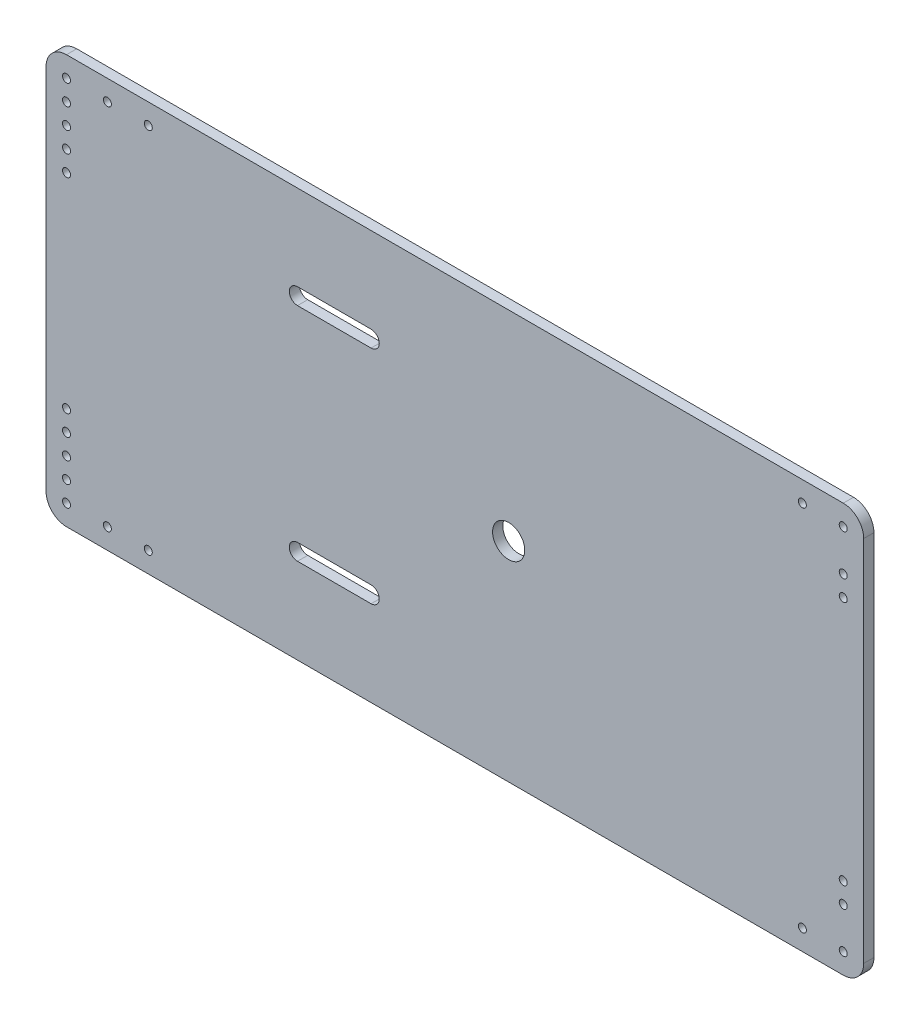
SolidWorks part; units mm, degrees
material "PC High Viscosity"
ref_plane "Front Plane" through (0, 0, 0) normal (0, 0, 1) x (1, 0, 0)
ref_plane "Top Plane" through (0, 0, 0) normal (0, 1, 0) x (1, 0, 0)
ref_plane "Right Plane" through (0, 0, 0) normal (1, 0, 0) x (0, 0, -1)
sketch "Sketch1" plane through (0, 0, 0) normal (0, 0, 1) x (1, 0, 0)
  line L1 (12.7, 0) -> (495.3, 0)
  line L2 (0, 12.7) -> (0, 241.3)
  line L3 (12.7, 254) -> (495.3, 254)
  line L4 (508, 12.7) -> (508, 241.3)
  arc A0 (495.3, 254) -> (508, 241.3) centre (495.3, 241.3) cw
  arc A1 (495.3, 0) -> (508, 12.7) centre (495.3, 12.7) ccw
  arc A2 (12.7, 0) -> (0, 12.7) centre (12.7, 12.7) cw
  arc A3 (0, 241.3) -> (12.7, 254) centre (12.7, 241.3) cw
  point P7 (508, 254)
  point P10 (508, 0)
  point P13 (0, 0)
  point P16 (0, 254)
  dimension "D3" = 12.7
  dimension "D1" = 508
  dimension "D2" = 254
extrude "Boss-Extrude1" add sketch "Sketch1" along normal blind 6.35
sketch "Sketch2" plane through (0, 0, 6.35) normal (0, 0, 1) x (1, 0, 0)
  line L10 (495.3, 254) -> (12.7, 254) construction
  line L11 (0, 241.3) -> (0, 12.7) construction
  line L12 (-20.2403, 127) -> (522.5431, 127) construction
  circle A6 centre (12.7, 190.5) radius 2.5
  circle A7 centre (12.7, 203.2) radius 2.5
  circle A8 centre (12.7, 215.9) radius 2.5
  circle A9 centre (12.7, 228.6) radius 2.5
  circle A10 centre (12.7, 241.3) radius 2.4892
  circle A11 centre (38.1, 241.3) radius 2.4892
  circle A12 centre (63.5, 241.3) radius 2.4892
  circle A13 centre (63.5, 12.7) radius 2.4892
  circle A14 centre (38.1, 12.7) radius 2.4892
  circle A15 centre (12.7, 63.5) radius 2.5
  circle A16 centre (12.7, 50.8) radius 2.5
  circle A17 centre (12.7, 38.1) radius 2.5
  circle A18 centre (12.7, 25.4) radius 2.5
  circle A19 centre (12.7, 12.7) radius 2.4892
  dimension "D2" = 12.7
  dimension "D3" = 5
  dimension "D4" = 4.9784
  dimension "D5" = 4.9784
  dimension "D6" = 4.9784
  dimension "D7" = 5
  dimension "D8" = 5
  dimension "D9" = 5
  dimension "D10" = 12.7
  dimension "D11" = 127
  dimension "D12" = 25.4
  dimension "D13" = 25.4
  dimension "D14" = 12.7
  dimension "D15" = 12.7
  dimension "D16" = 12.7
  dimension "D17" = 12.7
extrude "Cut-Extrude1" cut sketch "Sketch2" against normal through all
sketch "Sketch3" plane through (0, 0, 6.35) normal (0, 0, 1) x (1, 0, 0)
  line L8 (495.3, 254) -> (12.7, 254) construction
  line L11 (508, 12.7) -> (508, 241.3) construction
  line L12 (-50.4543, 127) -> (582.5907, 127) construction
  circle A0 centre (469.8795, 241.3) radius 2.4892
  circle A1 centre (495.2795, 241.3) radius 2.4892
  circle A4 centre (495.2795, 215.9) radius 2.4892
  circle A5 centre (495.2795, 203.2) radius 2.4892
  circle A16 centre (469.8795, 12.7) radius 2.4892
  circle A17 centre (495.2795, 12.7) radius 2.4892
  circle A18 centre (495.2795, 38.1) radius 2.4892
  circle A19 centre (495.2795, 50.8) radius 2.4892
  dimension "D1" = 4.9784
  dimension "D2" = 4.9784
  dimension "D3" = 12.7
  dimension "D4" = 12.7205
  dimension "D5" = 127
  dimension "D10" = 25.4
  dimension "D13" = 25.4
  dimension "D15" = 12.7
extrude "Cut-Extrude2" cut sketch "Sketch3" against normal through all
sketch "Sketch4" plane through (0, 0, 6.35) normal (0, 0, 1) x (1, 0, 0)
  line L0 (495.3, 254) -> (12.7, 254) construction
  line L1 (101.6, 178.054) -> (256.6, 178.054) construction
  line L2 (101.6, 178.054) -> (101.6, 76.054) construction
  line L3 (101.6, 76.054) -> (256.6, 76.054) construction
  line L4 (256.6, 178.054) -> (256.6, 76.054) construction
  line L6 (0, 241.3) -> (0, 12.7) construction
  line L7 (156.21, 195.834) -> (201.93, 195.834) construction
  line L8 (156.21, 200.914) -> (201.93, 200.914)
  line L9 (156.21, 190.754) -> (201.93, 190.754)
  line L10 (156.21, 58.274) -> (201.93, 58.274) construction
  line L11 (156.21, 63.354) -> (201.93, 63.354)
  line L12 (156.21, 53.194) -> (201.93, 53.194)
  arc A0 (156.21, 200.914) -> (156.21, 190.754) centre (156.21, 195.834) ccw
  arc A1 (201.93, 190.754) -> (201.93, 200.914) centre (201.93, 195.834) ccw
  arc A2 (156.21, 63.354) -> (156.21, 53.194) centre (156.21, 58.274) ccw
  arc A3 (201.93, 53.194) -> (201.93, 63.354) centre (201.93, 58.274) ccw
  point P10 (179.07, 195.834)
  point P15 (179.07, 58.274)
  dimension "D7" = 5.08
  dimension "D9" = 5.08
  dimension "D1" = 155
  dimension "D2" = 102
  dimension "D3" = 75.946
  dimension "D4" = 101.6
  dimension "D5" = 77.47
  dimension "D6" = 45.72
  dimension "D8" = 45.72
  dimension "D10" = 12.7
  dimension "D11" = 12.7
extrude "Cut-Extrude3" cut sketch "Sketch4" against normal through all
sketch "Sketch5" plane through (0, 0, 6.35) normal (0, 0, 1) x (1, 0, 0)
  line L0 (307.5263, 284.1622) -> (307.5263, -18.394) construction
  line L1 (508, 12.7) -> (508, 241.3) construction
  line L2 (12.7, 0) -> (495.3, 0) construction
  line L3 (0, 241.3) -> (0, 12.7) construction
  circle A0 centre (287.4065, 129.6573) radius 10
  dimension "D3" = 129.6573
  dimension "15mm" = 20
  dimension "D1" = 200.4737
  dimension "D2" = 302.5562
  dimension "D4" = 287.4065
extrude "Cut-Extrude4" cut sketch "Sketch5" against normal through all
sketch "Sketch6" plane through (0, 0, 6.35) normal (0, 0, 1) x (1, 0, 0)
  line L0 (-1009.6524, 0) -> (48990.3476, 0) construction
  line L1 (0, -1011.952) -> (0, 48988.048) construction
  point P3 (0, 0)
  point P5 (-52.4069, 0)
  point P6 (0, 0)
